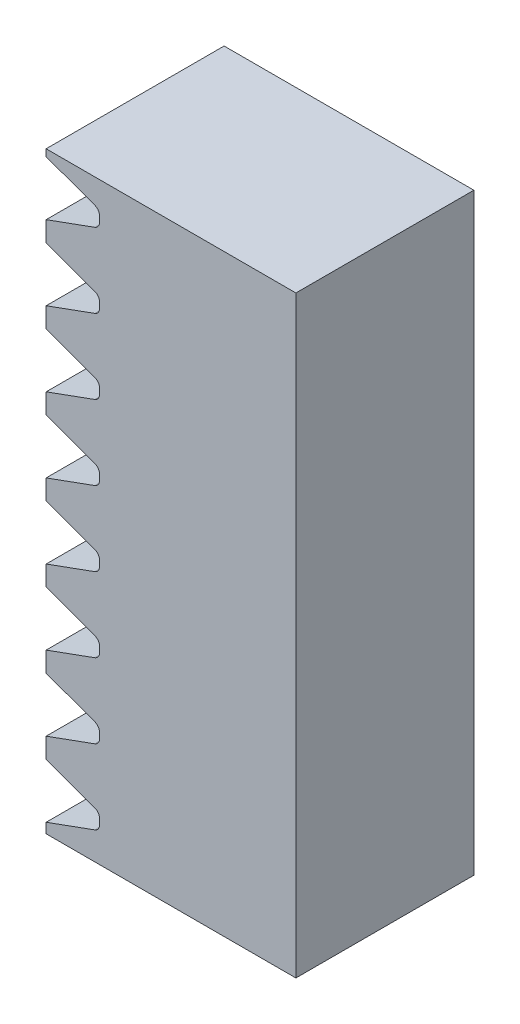
SolidWorks part; units mm, degrees
ref_plane "Front Plane" through (0, 0, 0) normal (0, 0, 1) x (1, 0, 0)
ref_plane "Top Plane" through (0, 0, 0) normal (0, 1, 0) x (1, 0, 0)
ref_plane "Right Plane" through (0, 0, 0) normal (1, 0, 0) x (0, 0, -1)
ref_axis "Axis1" through (0, -55, 0) along (0, 1, 0)
sketch "SketchCI.m_strSketchName" plane through (0, 0, 0) normal (0, 0, 1) x (1, 0, 0)
  line L0 (-2, 3.1416) -> (-2, -191.6371)
  line L1 (-2, -191.6371) -> (19.05, -191.6371)
  line L2 (19.05, -191.6371) -> (19.05, 3.1416)
  line L3 (19.05, 3.1416) -> (-2, 3.1416)
  dimension "D1" = 2
  dimension "D2" = 191.6371
  dimension "D3" = 19.05
  dimension "D4" = 3.1416
extrude "拉伸CI" add sketch "SketchCI.m_strSketchName" along normal blind 7.5 and the other way blind 7.5
sketch "齿草图大直齿轮" plane through (0, 0, 0) normal (0, 0, 1) x (1, 0, 0)
  line L0 (-2, 2.2987) -> (-2, -2.2987)
  line L1 (-2, -2.2987) -> (2.1052, -0.8046)
  line L2 (2.5, -0.2407) -> (2.5, 0.2407)
  line L3 (2.1052, 0.8046) -> (-2, 2.2987)
  arc A0 (2.1052, -0.8046) -> (2.5, -0.2407) centre (1.9, -0.2407) ccw
  arc A1 (2.5, 0.2407) -> (2.1052, 0.8046) centre (1.9, 0.2407) ccw
  dimension "D1" = 1.2
  dimension "D2" = 1.2
  dimension "齿顶高" = 2
  dimension "FLANKONE" = 1.4761
  dimension "FLANKONEANGLE" = 70
  dimension "齿根高" = 2.5
  dimension "FLANKTWO" = 1.4761
  dimension "FLANKTWOANGLE" = 70
extrude "齿拉伸切除大直齿轮" cut sketch "齿草图大直齿轮" against normal blind 7.5 and the other way blind 7.5
pattern_linear "齿形大直齿轮" count 31 spacing 6.2832 along (0, -1, 0) of "齿拉伸切除大直齿轮"
sketch "辅助草图大直齿轮" plane through (0, 0, 0) normal (0, 0, 1) x (1, 0, 0)
  line L0 (0, 0) -> (0, -194.7787) construction
sketch "Sketch4" plane through (0, 0, 7.5) normal (0, 0, 1) x (1, 0, 0)
  line L0 (19.05, -141.6371) -> (-18.2754, -141.6371)
  line L1 (19.05, -191.6371) -> (19.05, 3.1416) construction
  line L2 (-2, -191.6371) -> (19.05, -191.6371) construction
  dimension "D1" = 50
extrude "Extrude3" cut sketch "Sketch4" against normal through all and the other way through all flip side to cut
